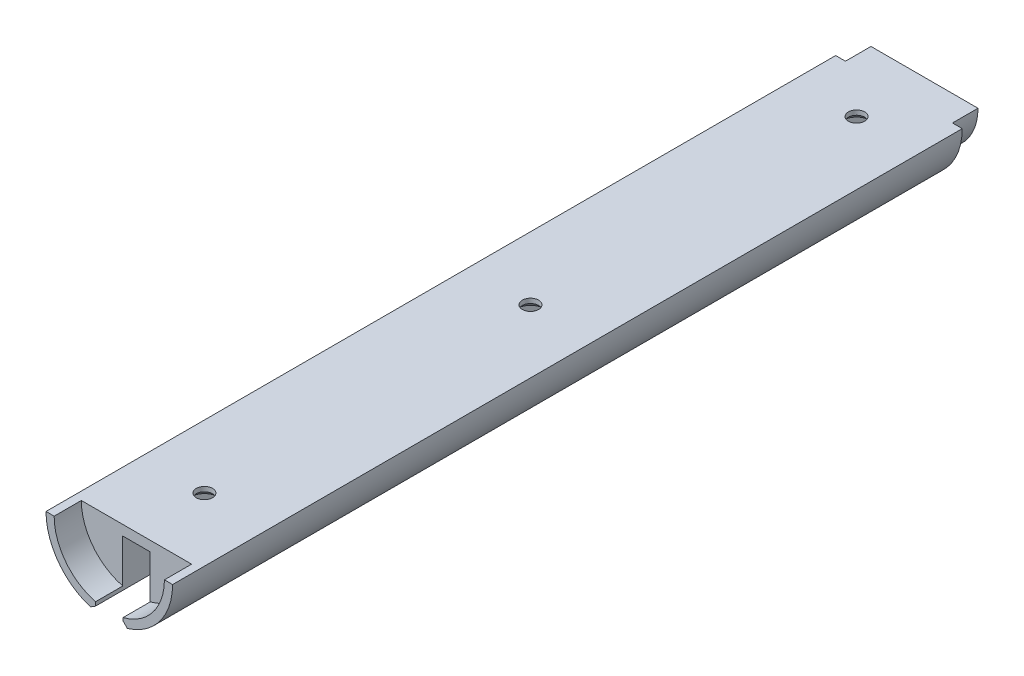
SolidWorks part; units mm, degrees
ref_plane "Front Plane" through (0, 0, 0) normal (0, 0, 1) x (1, 0, 0)
ref_plane "Top Plane" through (0, 0, 0) normal (0, 1, 0) x (1, 0, 0)
ref_plane "Right Plane" through (0, 0, 0) normal (1, 0, 0) x (0, 0, -1)
sketch "Sketch1" plane through (0, 0, 0) normal (0, 0, 1) x (1, 0, 0)
  line L1 (-14.7902, 8.509) -> (14.7902, 8.509)
  line L2 (3.0226, 5.969) -> (-3.0226, 5.969) construction
  line L11 (3.2131, -6.1595) -> (3.2131, 6.1595)
  line L12 (3.2131, 6.1595) -> (-3.2131, 6.1595)
  line L13 (-3.2131, 6.1595) -> (-3.2131, -6.1595)
  line L14 (-3.2131, -6.1595) -> (3.2131, -6.1595)
  line L15 (3.2131, -6.1595) -> (3.2131, 6.1595)
  line L16 (3.2131, 6.1595) -> (-3.2131, 6.1595)
  line L17 (-3.2131, 6.1595) -> (-3.2131, -6.1595)
  line L18 (-3.2131, -6.1595) -> (3.2131, -6.1595)
  arc A0 (-14.7902, 8.509) -> (14.7902, 8.509) centre (0, 8.509) ccw
  dimension "D1" = 2.54
  dimension "D2" = 0.1905
extrude "Boss-Extrude1" add sketch "Sketch1" along normal mid plane 190.5 contours L1 A0 L17 L16 L15 region at (0, 8.1798, 0)
sketch "Sketch2" plane through (0, 0, 95.25) normal (0, 0, 1) x (1, 0, 0)
  line L0 (-14.7902, 8.509) -> (14.7902, 8.509) construction
  line L1 (-12.8852, 8.509) -> (12.8852, 8.509)
  circle A0 centre (0, 8.509) radius 12.8852
  arc A2 (-14.7902, 8.509) -> (-3.2131, -5.9279) centre (0, 8.509) ccw construction
  line M2 (14.7902, 8.509) -> (-14.7902, 8.509)
  line M4 (-3.2131, -5.9279) -> (-3.2131, 6.1595)
  line M5 (-3.2131, 6.1595) -> (3.2131, 6.1595)
  line M6 (3.2131, 6.1595) -> (3.2131, -5.9279)
  dimension "D1" = 1.905
extrude "Cut-Extrude1" cut sketch "Sketch2" against normal blind 6.35 contours A0 M2 M4 M5 M6 region at (0, 8.2227, 95.25)
sketch "Sketch3" plane through (0, 0, -95.25) normal (0, 0, -1) x (-1, 0, 0)
  line L8 (12.8852, 8.509) -> (-12.8852, 8.509)
  line L9 (3.2131, 6.1595) -> (3.2131, -3.9691)
  line L10 (-3.2131, 6.1595) -> (3.2131, 6.1595)
  line L11 (-3.2131, -3.9691) -> (-3.2131, 6.1595)
  line L12 (12.8852, 8.509) -> (-12.8852, 8.509)
  line L13 (3.2131, 6.1595) -> (3.2131, -3.9691)
  line L14 (-3.2131, 6.1595) -> (3.2131, 6.1595)
  line L15 (-3.2131, -3.9691) -> (-3.2131, 6.1595)
  line L16 (14.7902, 8.509) -> (-14.7902, 8.509)
  line L17 (-3.2131, -5.9279) -> (-3.2131, 6.1595)
  line L18 (-3.2131, 6.1595) -> (3.2131, 6.1595)
  line L19 (3.2131, 6.1595) -> (3.2131, -5.9279)
  line L20 (14.7902, 8.509) -> (-14.7902, 8.509)
  line L21 (-3.2131, -5.9279) -> (-3.2131, 6.1595)
  line L22 (-3.2131, 6.1595) -> (3.2131, 6.1595)
  line L23 (3.2131, 6.1595) -> (3.2131, -5.9279)
  circle A2 centre (0, 8.509) radius 12.5042
  arc A4 (3.2131, -3.9691) -> (12.8852, 8.509) centre (0, 8.509) ccw
  arc A5 (-12.8852, 8.509) -> (-3.2131, -3.9691) centre (0, 8.509) ccw
  arc A6 (3.2131, -3.9691) -> (12.8852, 8.509) centre (0, 8.509) ccw
  arc A7 (-12.8852, 8.509) -> (-3.2131, -3.9691) centre (0, 8.509) ccw
  arc A9 (-14.7902, 8.509) -> (-3.2131, -5.9279) centre (0, 8.509) ccw
  arc A10 (3.2131, -5.9279) -> (14.7902, 8.509) centre (0, 8.509) ccw
  arc A11 (-14.7902, 8.509) -> (-3.2131, -5.9279) centre (0, 8.509) ccw
  arc A12 (3.2131, -5.9279) -> (14.7902, 8.509) centre (0, 8.509) ccw
  line M14 (14.7902, 8.509) -> (-14.7902, 8.509)
  arc M15 (-14.7902, 8.509) -> (-3.2131, -5.9279) centre (0, 8.509) ccw
  line M16 (-3.2131, -5.9279) -> (-3.2131, 6.1595)
  line M18 (3.2131, 6.1595) -> (3.2131, -5.9279)
  arc M19 (3.2131, -5.9279) -> (14.7902, 8.509) centre (0, 8.509) ccw
  dimension "D2" = 0.381
  dimension "D1" = 0
  dimension "D3" = 0
extrude "Cut-Extrude2" cut sketch "Sketch3" against normal blind 5.969 contours A6 M18 M19 M14 | A7 M14 M15 M16 | A7 A2 M14 M16 | L23 A6 A2 M14 region at (-10.0592, 0.7119, -95.25) region at (-13.8377, 8.3239, -95.25) region at (10.0381, 0.7912, -95.25) region at (10.3303, 0.5018, -95.25)
sketch "Sketch4" plane through (0, 6.1595, 0) normal (0, -1, 0) x (1, 0, 0)
  line L1 (0, -95.25) -> (0, 88.9) construction
  line L2 (3.2131, -95.25) -> (-3.2131, -95.25) construction
  line L3 (-3.2131, 88.9) -> (3.2131, 88.9) construction
  line L4 (0, -3.175) -> (-3.2131, -3.175) construction
  line L5 (-3.2131, 88.9) -> (-3.2131, -95.25) construction
  circle A0 centre (0, -79.375) radius 1.905
  circle A1 centre (0, 73.025) radius 1.905
  circle A2 centre (0, -3.175) radius 1.905
  dimension "D1" = 3.81
  dimension "D2" = 76.2
extrude "Cut-Extrude3" cut sketch "Sketch4" against normal through all
chamfer "Chamfer1" distance 1.27 angle 45 2 edges at (3.2131, -5.9279, 2.9845) (-3.2131, -5.9279, 2.9845) first distance on face at (3.2131, -1.8282, -0.0952) first distance on face at (-10.27, 0.2734, 2.9845)
chamfer "Chamfer2" distance 1.27 angle 45 3 edges at (0, 6.1595, 74.93) (0, 6.1595, -81.28) (0, 6.1595, -5.08)
sketch "Sketch5" plane through (-3.2131, 0, 0) normal (1, 0, 0) x (0, 0, -1)
  line L0 (53.2413, 3.6195) -> (-53.2413, 3.6195) construction
  line L1 (-88.9, 6.1595) -> (95.25, 6.1595) construction
  text T0 "<b>Ceiling LED Mount V1</b>" font "Century Gothic" height 3.81
  point P2 (0, 3.6195)
  dimension "D1" = 2.54
extrude "Cut-Extrude4" cut sketch "Sketch5" against normal blind 0.635
